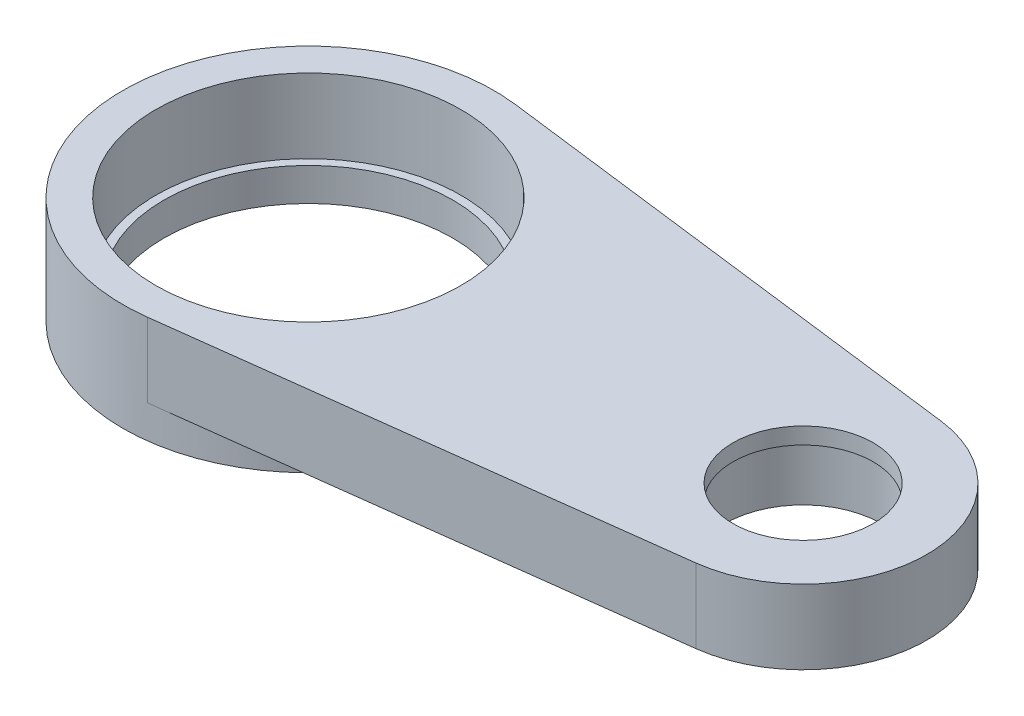
SolidWorks part; units mm, degrees
other "마크업1"
sketch "스케치8" plane through (80, 10, 22.5) normal (0.0741, 0.9433, 0.3234) x (0.9972, -0.0727, -0.0163)
sketch "스케치15" plane through (100, 13, 22.5) normal (0.0741, 0.9433, 0.3234) x (0.9972, -0.0727, -0.0163)
sketch "스케치16" plane through (100, 13, 22.5) normal (0.0741, 0.9433, 0.3234) x (0.9972, -0.0727, -0.0163)
material "7075-T6 (SN)"
ref_plane "정면" through (0, 0, 0) normal (0, 0, 1) x (1, 0, 0)
ref_plane "윗면" through (0, 0, 0) normal (0, 1, 0) x (1, 0, 0)
ref_plane "우측면" through (0, 0, 0) normal (1, 0, 0) x (0, 0, -1)
sketch "스케치1" plane through (0, 0, 0) normal (0, 1, 0) x (1, 0, 0)
  circle A0 centre (0, 0) radius 17.5
  circle A1 centre (0, 0) radius 22.5
  dimension "D1" = 35
  dimension "D2" = 45
extrude "보스-돌출1" add sketch "스케치1" along normal blind 8 contours A1 | A0
sketch "스케치2" plane through (0, 8, 0) normal (0, 1, 0) x (1, 0, 0)
  circle A0 centre (0, 0) radius 18.5
  circle A1 centre (0, 0) radius 22.5 construction
  circle A2 centre (0, 0) radius 22.5
  dimension "D1" = 37
extrude "보스-돌출2" add sketch "스케치2" along normal blind 5
sketch "스케치3" plane through (0, 13, 0) normal (0, 1, 0) x (1, 0, 0)
  line L0 (2.8125, 22.3235) -> (61.875, 14.8824)
  line L1 (0, 0) -> (60, 0) construction
  line L2 (2.8125, -22.3235) -> (61.875, -14.8824)
  circle A0 centre (0, 0) radius 22.5 construction
  arc A1 (2.8125, -22.3235) -> (2.8125, 22.3235) centre (0, 0) ccw
  arc A2 (61.875, -14.8824) -> (61.875, 14.8824) centre (60, 0) ccw
  dimension "D2" = 30
  dimension "D1" = 60
extrude "보스-돌출3" add sketch "스케치3" against normal blind 9
sketch "스케치7" plane through (0, 8, 0) normal (0, 1, 0) x (1, 0, 0)
  circle A0 centre (0, 0) radius 18.5 construction
  circle A1 centre (0, 0) radius 18.5
extrude "컷-돌출4" cut sketch "스케치7" against normal blind 4
sketch "스케치13" plane through (0, 4, 0) normal (0, -1, 0) x (1, 0, 0)
  circle A0 centre (60, 0) radius 9.5
  dimension "D1" = 19
extrude "컷-돌출9" cut sketch "스케치13" against normal blind 7
sketch "스케치14" plane through (0, 11, 0) normal (0, -1, 0) x (1, 0, 0)
  circle A0 centre (60, 0) radius 8.5
  dimension "D1" = 17
extrude "컷-돌출10" cut sketch "스케치14" against normal through all
